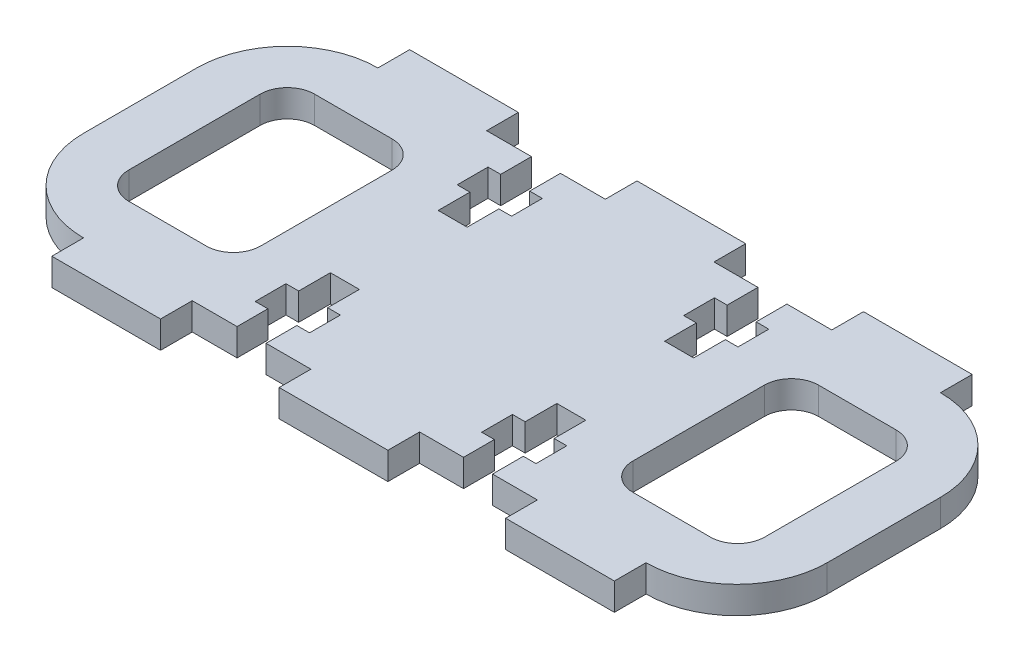
SolidWorks part; units mm, degrees
material "Thornel Mat VMA"
ref_plane "前视基准面" through (0, 0, 0) normal (0, 0, 1) x (1, 0, 0)
ref_plane "上视基准面" through (0, 0, 0) normal (0, 1, 0) x (1, 0, 0)
ref_plane "右视基准面" through (0, 0, 0) normal (1, 0, 0) x (0, 0, -1)
sketch "草图1" plane through (0, 0, 0) normal (0, 1, 0) x (1, 0, 0)
  line L0 (10, 0) -> (10, -3.5)
  line L1 (0, 0) -> (10, 0)
  line L2 (0, 0) -> (0, 32.5)
  line L3 (0, 32.5) -> (10, 32.5)
  line L4 (82.1, 0) -> (82.1, 32.5)
  line L5 (10, -3.5) -> (22, -3.5)
  line L6 (22, -3.5) -> (22, 0)
  line L7 (26.95, 0) -> (26.95, 3.4)
  line L8 (26.95, 3.4) -> (25.55, 3.4)
  line L9 (25.55, 3.4) -> (25.55, 6.8)
  line L10 (25.55, 6.8) -> (26.95, 6.8)
  line L11 (26.95, 6.8) -> (26.95, 10.3)
  line L12 (26.95, 10.3) -> (30.15, 10.3)
  line L13 (30.15, 10.3) -> (30.15, 6.8)
  line L14 (30.15, 6.8) -> (31.55, 6.8)
  line L15 (31.55, 6.8) -> (31.55, 3.4)
  line L16 (31.55, 3.4) -> (30.15, 3.4)
  line L17 (30.15, 3.4) -> (30.15, 0)
  line L18 (28.55, -0.9012) -> (28.55, 13.2859) construction
  line L19 (22, 0) -> (26.95, 0)
  line L20 (30.15, 0) -> (35.1, 0)
  line L21 (35.1, 0) -> (35.1, -3.5)
  line L22 (35.1, -3.5) -> (47.1, -3.5)
  line L23 (47.1, -3.5) -> (47.1, 0)
  line L24 (47.1, 0) -> (51.95, 0)
  line L25 (0, 16.25) -> (82.1, 16.25) construction
  line L26 (28.55, 33.4012) -> (28.55, 19.2141) construction
  line L27 (30.15, 29.1) -> (30.15, 32.5)
  line L28 (31.55, 29.1) -> (30.15, 29.1)
  line L29 (31.55, 25.7) -> (31.55, 29.1)
  line L30 (30.15, 25.7) -> (31.55, 25.7)
  line L31 (30.15, 22.2) -> (30.15, 25.7)
  line L32 (26.95, 22.2) -> (30.15, 22.2)
  line L33 (26.95, 25.7) -> (26.95, 22.2)
  line L34 (25.55, 25.7) -> (26.95, 25.7)
  line L35 (25.55, 29.1) -> (25.55, 25.7)
  line L36 (50.65, 3.4) -> (50.65, 6.8) [skipped]
  line L37 (50.65, 6.8) -> (52.05, 6.8) [skipped]
  line L38 (52.05, 6.8) -> (52.05, 10.3) [skipped]
  line L39 (56.65, 3.4) -> (55.25, 3.4) [skipped]
  line L40 (56.65, 6.8) -> (56.65, 3.4) [skipped]
  line L41 (55.25, 6.8) -> (56.65, 6.8) [skipped]
  line L42 (55.25, 10.3) -> (55.25, 6.8) [skipped]
  line L43 (52.05, 10.3) -> (55.25, 10.3) [skipped]
  line L44 (52.05, 0) -> (52.05, 3.4) [skipped]
  line L45 (55.25, 3.4) -> (55.25, 0) [skipped]
  line L46 (26.95, 29.1) -> (25.55, 29.1)
  line L47 (26.95, 32.5) -> (26.95, 29.1)
  line L48 (47.1, 36) -> (47.1, 32.5)
  line L49 (35.1, 36) -> (47.1, 36)
  line L50 (35.1, 32.5) -> (35.1, 36)
  line L51 (22, 36) -> (22, 32.5)
  line L52 (10, 36) -> (22, 36)
  line L53 (10, 32.5) -> (10, 36)
  line L54 (22, 32.5) -> (26.95, 32.5)
  line L55 (30.15, 32.5) -> (35.1, 32.5)
  line L56 (47.1, 32.5) -> (51.95, 32.5)
  line L57 (51.95, 0) -> (51.95, 3.4)
  line L58 (51.95, 3.4) -> (50.55, 3.4)
  line L59 (50.55, 3.4) -> (50.55, 6.8)
  line L60 (50.55, 6.8) -> (51.95, 6.8)
  line L61 (51.95, 6.8) -> (51.95, 10.3)
  line L62 (51.95, 10.3) -> (55.15, 10.3)
  line L63 (55.15, 10.3) -> (55.15, 6.8)
  line L64 (55.15, 6.8) -> (56.55, 6.8)
  line L65 (56.55, 6.8) -> (56.55, 3.4)
  line L66 (56.55, 3.4) -> (55.15, 3.4)
  line L67 (55.15, 3.4) -> (55.15, 0)
  line L68 (53.55, -0.9012) -> (53.55, 13.2859) construction
  line L69 (60.1, 0) -> (60.1, -3.5)
  line L70 (60.1, -3.5) -> (72.1, -3.5)
  line L71 (72.1, -3.5) -> (72.1, 0)
  line L72 (55.15, 29.1) -> (55.15, 32.5)
  line L73 (56.55, 29.1) -> (55.15, 29.1)
  line L74 (56.55, 25.7) -> (56.55, 29.1)
  line L75 (55.15, 25.7) -> (56.55, 25.7)
  line L76 (55.15, 22.2) -> (55.15, 25.7)
  line L77 (51.95, 22.2) -> (55.15, 22.2)
  line L78 (51.95, 25.7) -> (51.95, 22.2)
  line L79 (50.55, 25.7) -> (51.95, 25.7)
  line L80 (50.55, 29.1) -> (50.55, 25.7)
  line L81 (51.95, 29.1) -> (50.55, 29.1)
  line L82 (51.95, 32.5) -> (51.95, 29.1)
  line L83 (72.1, 36) -> (72.1, 32.5)
  line L84 (60.1, 36) -> (72.1, 36)
  line L85 (60.1, 32.5) -> (60.1, 36)
  line L86 (55.15, 32.5) -> (60.1, 32.5)
  line L87 (55.15, 0) -> (60.1, 0)
  line L88 (72.1, 0) -> (82.1, 0)
  line L89 (72.1, 32.5) -> (82.1, 32.5)
  dimension "D1" = 3.5
  dimension "D2" = 12
  dimension "D3" = 10
  dimension "D4" = 4.95
  dimension "D5" = 3.2
  dimension "D6" = 3.4
  dimension "D7" = 3.4
  dimension "D8" = 3.5
  dimension "D9" = 6
  dimension "D10" = 32.5
  dimension "D11" = 10
  dimension "D13" = 4.95
  dimension "D14" = 2
  dimension "D16" = 25
  dimension "D17" = 25
  dimension "D12" = 2
  dimension "D15" = 2
extrude "凸台-拉伸1" add sketch "草图1" along normal blind 3
fillet "圆角1" radius 10 4 edges at (0, 1.5, -32.5) (82.1, 1.5, -32.5) (82.1, 1.5, 0) (0, 1.5, 0)
sketch "草图2" plane through (0, 0, 0) normal (0, -1, 0) x (1, 0, 0)
  line L0 (41.1, -36) -> (41.1, 3.5) construction
  line L5 (6, -6) -> (20.55, -6)
  line L6 (6, -6) -> (6, -26.5)
  line L7 (6, -26.5) -> (20.55, -26.5)
  line L8 (20.55, -6) -> (20.55, -26.5)
  line L9 (47.1, -36) -> (35.1, -36) construction
  line L10 (35.1, 3.5) -> (47.1, 3.5) construction
  line L14 (26.95, -32.5) -> (22, -32.5) construction
  line L15 (0, -22.5) -> (0, -10) construction
  line L16 (22, 0) -> (26.95, 0) construction
  line L17 (25.55, -25.7) -> (25.55, -29.1) construction
  line L18 (61.65, -6) -> (61.65, -26.5)
  line L19 (76.2, -26.5) -> (61.65, -26.5)
  line L20 (76.2, -6) -> (76.2, -26.5)
  line L21 (76.2, -6) -> (61.65, -6)
  dimension "D4" = 6
  dimension "D5" = 6
  dimension "D6" = 6
  dimension "D7" = 5
extrude "切除-拉伸1" cut sketch "草图2" against normal through all
fillet "圆角2" radius 3 8 edges at (76.2, 1.5, -26.5) (61.65, 1.5, -26.5) (61.65, 1.5, -6) (76.2, 1.5, -6) (6, 1.5, -6) (20.55, 1.5, -6) (20.55, 1.5, -26.5) (6, 1.5, -26.5)
